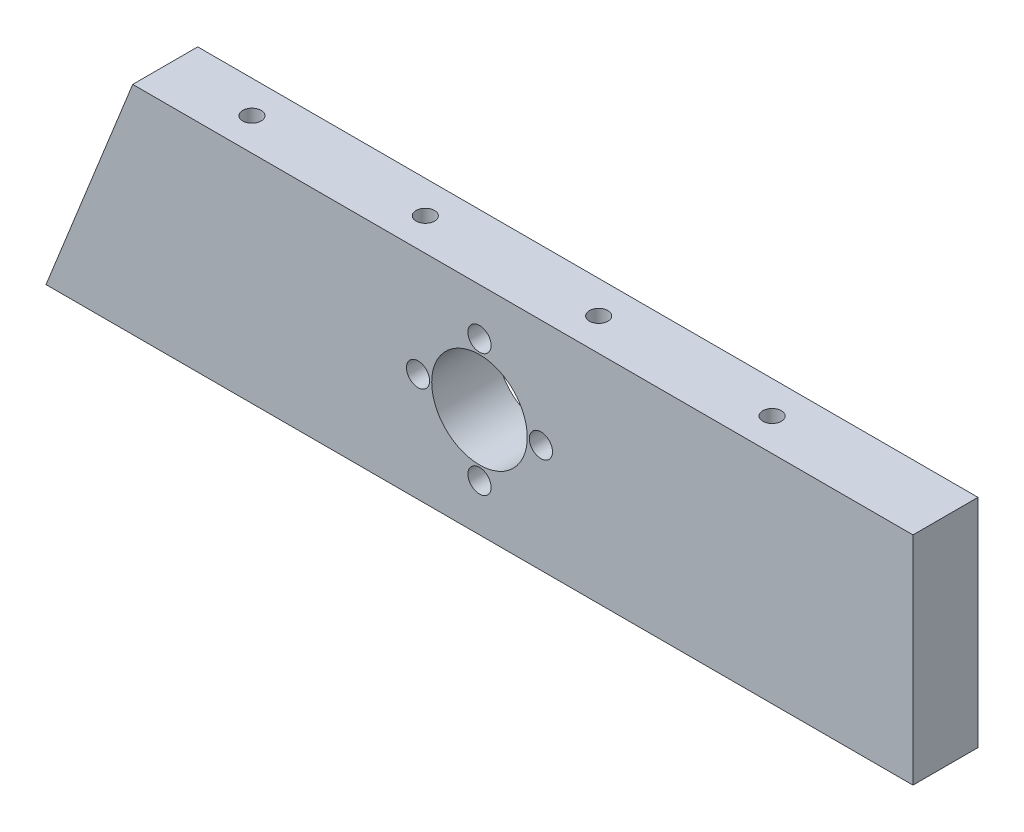
SolidWorks part; units mm, degrees
material "PE High Density Film"
ref_plane "Front Plane" through (0, 0, 0) normal (0, 0, 1) x (1, 0, 0)
ref_plane "Top Plane" through (0, 0, 0) normal (0, 1, 0) x (1, 0, 0)
ref_plane "Right Plane" through (0, 0, 0) normal (1, 0, 0) x (0, 0, -1)
sketch "Sketch1" plane through (0, 0, 0) normal (0, 0, 1) x (1, 0, 0)
  line L1 (-50.8, 15.875) -> (63.5, 15.875)
  line L2 (-50.8, 15.875) -> (-63.5, -15.875)
  line L3 (-63.5, -15.875) -> (63.5, -15.875)
  line L4 (63.5, 15.875) -> (63.5, -15.875)
  circle A0 centre (0, -9) radius 1.7
  circle A1 centre (-9, 0) radius 1.7
  circle A2 centre (0, 9) radius 1.7
  circle A3 centre (9, 0) radius 1.7
  arc A8 (-5.3578, -2.967) -> (-5.3172, -2.9531) centre (-6.35, 0) ccw construction
  circle A16 centre (0, 0) radius 7
  circle A17 centre (0, 0) radius 9 construction
  point P0 (0, 0)
  dimension "D3" = 3.4
  dimension "D5" = 14
  dimension "D1" = 127
  dimension "D2" = 31.75
  dimension "D8" = 114.3
  dimension "D11" = 9
  dimension "D4" = 63.5
extrude "Boss-Extrude1" add sketch "Sketch1" along normal blind 9.525
hole_wizard "Tap Drill for #6-32 Tap1" positions "Sketch11" profile "Sketch12" hole size "#6-32" standard "ANSI Inch"
sketch "Sketch11" plane through (0, -15.875, 0) normal (0, -1, 0) x (-1, 0, 0)
  line L0 (-63.5, -9.525) -> (-63.5, 0) construction
  line L1 (63.5, -9.525) -> (-63.5, -9.525) construction
  point P0 (-38.1, -4.7625)
  dimension "D1" = 25.4
  dimension "D2" = 4.7625
sketch "Sketch12" plane through (38.1, -15.875, 4.7625) normal (1, 0, 0) x (0, 0, -1)
  line L0 (0, 0) -> (0, 13.5127)
  line L1 (0, 13.5127) -> (1.3525, 12.7)
  line L2 (1.3525, 12.7) -> (1.3525, 0)
  line L5 (1.3525, 0) -> (0, 0)
  line L10 (0, 13.5127) -> (-1.3526, 12.7) construction
  line L11 (0, -6.35) -> (0, 107.95) construction
  dimension "Hole Dia." = 2.7051
  dimension "Hole Depth" = 12.7
  dimension "Drill Angle" = 118
pattern_linear "LPattern1" count 4 spacing 25.4 along (-1, 0, 0) of "Tap Drill for #6-32 Tap1"
mirror "Mirror8" about plane through (0, 0, 0) normal (0, 1, 0) of "Tap Drill for #6-32 Tap1", "LPattern1"
equation "\"Plate Screw Hole Diameter\"= 0.116in"
equation "\"Plate Width\"= 5in"
equation "\"Plate Thickness\"= .375in"
equation "\"Num holes\"= 4"
equation "\"Plate Height\"= 1.25in"
equation "\"D1@Sketch11\"=\"Plate Width\" / ( \"Num holes\" + 1)"
equation "\"D2@Sketch11\"=\"Plate Thickness\"/2"
equation "\"D3@LPattern1\"=\"Plate Width\" / ( \"Num holes\"  + 1 )"
equation "\"D1@Sketch1\"=\"Plate Width\""
equation "\"D2@Sketch1\"=\"Plate Height\""
equation "\"D4@Sketch1\"= \"Plate Width\"/2"
